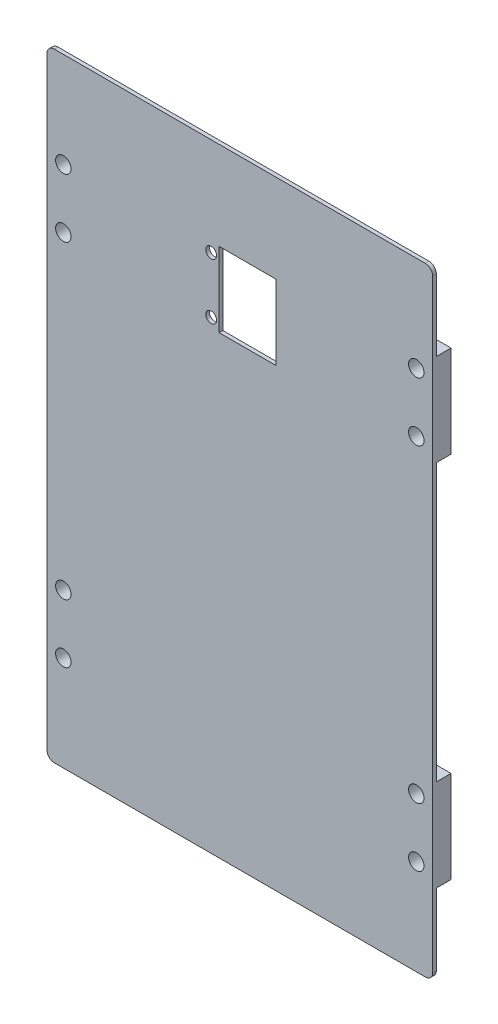
SolidWorks part; units mm, degrees
ref_plane "Front Plane" through (0, 0, 0) normal (0, 0, 1) x (1, 0, 0)
ref_plane "Top Plane" through (0, 0, 0) normal (0, 1, 0) x (1, 0, 0)
ref_plane "Right Plane" through (0, 0, 0) normal (1, 0, 0) x (0, 0, -1)
sketch "Sketch1" plane through (0, 0, 0) normal (0, 0, 1) x (1, 0, 0)
  line L1 (0, -100.2) -> (104.9, -100.2)
  line L2 (0, -100.2) -> (0, 67.9)
  line L3 (0, 67.9) -> (104.9, 67.9)
  line L4 (104.9, -100.2) -> (104.9, 67.9)
extrude "Boss-Extrude1" add sketch "Sketch1" along normal blind 1 from offset 4
sketch "Sketch2" plane through (0, 0, 4) normal (0, 0, -1) x (-1, 0, 0)
  line L0 (-100.45, -58.25) -> (-100.45, -74.25) construction
  line L1 (-4.45, -58.25) -> (-4.45, -74.25) construction
  line L2 (-100.45, 41.95) -> (-100.45, 25.95) construction
  line L3 (-4.45, 41.95) -> (-4.45, 25.95) construction
  line L4 (-104.9, -100.2) -> (-104.9, 67.9) construction
  line L5 (-104.9, 46.45) -> (-96, 46.45)
  line L6 (-104.9, 46.45) -> (-104.9, 21.45)
  line L7 (-104.9, 21.45) -> (-96, 21.45)
  line L8 (-96, 46.45) -> (-96, 21.45)
  line L9 (0, 67.9) -> (0, -100.2) construction
  line L10 (0, 46.45) -> (-8.9, 46.45)
  line L11 (0, 46.45) -> (0, 21.45)
  line L12 (0, 21.45) -> (-8.9, 21.45)
  line L13 (-8.9, 46.45) -> (-8.9, 21.45)
  line L15 (0, -53.75) -> (-8.9, -53.75)
  line L16 (0, -53.75) -> (0, -78.75)
  line L17 (0, -78.75) -> (-8.9, -78.75)
  line L18 (-8.9, -53.75) -> (-8.9, -78.75)
  line L19 (-104.9, -53.75) -> (-96, -53.75)
  line L20 (-104.9, -53.75) -> (-104.9, -78.75)
  line L21 (-104.9, -78.75) -> (-96, -78.75)
  line L22 (-96, -53.75) -> (-96, -78.75)
  circle A1 centre (-100.45, -74.25) radius 1.95 construction
  circle A2 centre (-100.45, -58.25) radius 1.95 construction
  circle A3 centre (-4.45, -74.25) radius 1.95 construction
  circle A4 centre (-4.45, -58.25) radius 1.95 construction
  circle A5 centre (-4.45, 25.95) radius 1.95 construction
  circle A6 centre (-4.45, 41.95) radius 1.95 construction
  circle A7 centre (-100.45, 25.95) radius 1.95 construction
  circle A8 centre (-100.45, 41.95) radius 1.95 construction
  circle A9 centre (-100.45, -74.25) radius 1.95 construction
  circle A10 centre (-100.45, -58.25) radius 1.95 construction
  circle A11 centre (-4.45, -74.25) radius 1.95 construction
  circle A12 centre (-4.45, -58.25) radius 1.95 construction
  circle A13 centre (-4.45, 25.95) radius 1.95 construction
  circle A14 centre (-4.45, 41.95) radius 1.95 construction
  circle A15 centre (-100.45, 25.95) radius 1.95 construction
  circle A16 centre (-100.45, 41.95) radius 1.95 construction
  point P36 (-4.45, 33.95)
  point P37 (-8.9, 33.95)
  point P38 (-100.45, 33.95)
  point P39 (-96, 33.95)
  point P40 (-4.45, -66.25)
  point P41 (-8.9, -66.25)
  point P42 (-100.45, -66.25)
  point P43 (-96, -66.25)
  point P44 (-100.45, -78.75)
  dimension "D1" = 25
extrude "Boss-Extrude2" add sketch "Sketch2" along normal up to surface (4 mm away)
sketch "Sketch5" plane through (0, 0, 5) normal (0, 0, 1) x (1, 0, 0)
  circle A0 centre (100.45, -74.25) radius 2.1
  circle A1 centre (100.45, -58.25) radius 2.1
  circle A2 centre (4.45, -74.25) radius 2.1
  circle A3 centre (4.45, -58.25) radius 2.1
  circle A4 centre (4.45, 25.95) radius 2.1
  circle A5 centre (4.45, 41.95) radius 2.1
  circle A6 centre (100.45, 25.95) radius 2.1
  circle A7 centre (100.45, 41.95) radius 2.1
  dimension "D1" = 4.2
extrude "Cut-Extrude5" cut sketch "Sketch5" against normal through all
sketch "Sketch3" plane through (0, 0, 5) normal (0, 0, 1) x (1, 0, 0)
  line L0 (104.9, 67.9) -> (0, 67.9) construction
  line L1 (62.356, 43.856) -> (42.036, 43.856) construction
  line L2 (62.356, 43.856) -> (62.356, 23.536) construction
  line L3 (62.356, 23.536) -> (42.036, 23.536) construction
  line L4 (42.036, 43.856) -> (42.036, 23.536) construction
  line L5 (100.45, 25.95) -> (100.45, 41.95) construction
  line L6 (44.661, 41.316) -> (44.661, 26.076) construction
  line L7 (62.356, 23.536) -> (46.836, 23.536)
  line L8 (62.356, 23.536) -> (62.356, 43.856)
  line L9 (62.356, 43.856) -> (46.836, 43.856)
  line L10 (46.836, 23.536) -> (46.836, 43.856)
  circle A1 centre (44.661, 26.076) radius 1.475
  circle A2 centre (44.661, 41.316) radius 1.475
  point P4 (52.45, 33.95)
  point P5 (100.45, 33.95)
  point P10 (52.45, 67.9)
  point P15 (42.036, 33.696)
  point P16 (44.661, 33.696)
  dimension "D6" = 2.95
  dimension "D1" = 10.414
  dimension "D2" = 20.32
  dimension "D3" = 20.32
  dimension "D4" = 9.906
  dimension "D5" = 4.8
  dimension "D7" = 2.625
  dimension "D8" = 15.24
extrude "Cut-Extrude3" cut sketch "Sketch3" against normal up to next
fillet "Fillet1" radius 2 4 edges at (0, 67.9, 4.5) (0, -100.2, 4.5) (104.9, -100.2, 4.5) (104.9, 67.9, 4.5)
equation "\"width\"= 24"
equation "\"thk\"= 3"
equation "\"holesize\"= 4.2"
equation "\"holedistance\"= ( 20 + 12 ) / 2"
equation "\"threaded_hole\"= 3.9"
equation "\"fillet_radius\"= 2"
equation "\"ground_clearance\"= 25"
equation "\"tire_thk\"= 4"
equation "\"innerwheel_diam\" = \"wheel_diam\"-2*\"tire_thk\""
equation "\"innerwheel_thk\"= 8"
equation "\"wheel_diam\"= 2*(\"width\"/2+\"ground_clearance\")"
equation "\"D1@Sketch5\"=\"holesize\""
equation "\"coloursensor_holesize\"= 2.65"
equation "\"D6@Sketch3\"=\"coloursensor_holesize\"+0.3"
equation "\"D1@Fillet1\"=\"fillet_radius\""
